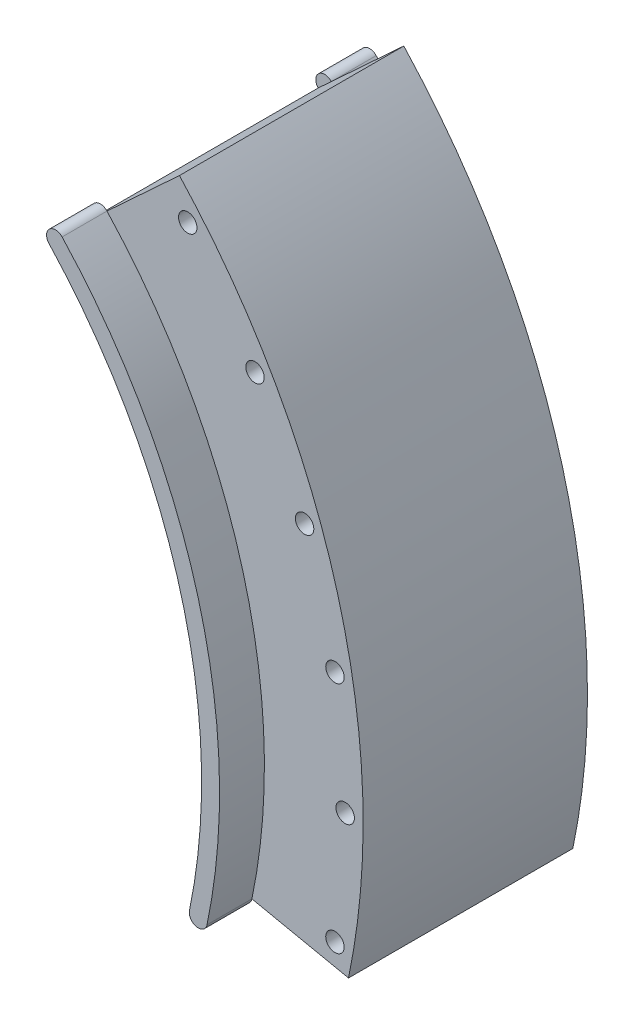
SolidWorks part; units mm, degrees
material "ABS"
ref_plane "Front Plane" through (0, 0, 0) normal (0, 0, 1) x (1, 0, 0)
ref_plane "Top Plane" through (0, 0, 0) normal (0, 1, 0) x (1, 0, 0)
ref_plane "Right Plane" through (0, 0, 0) normal (1, 0, 0) x (0, 0, -1)
sketch "Sketch1" plane through (0, 0, 0) normal (0, 0, 1) x (1, 0, 0)
  line L0 (0, 0) -> (203.2, 0) construction
  line L1 (203.2, 0) -> (209.55, 0) construction
  line L2 (148.1742, 148.1742) -> (143.6841, 143.6841) construction
  line L3 (143.6841, 143.6841) -> (0, 0) construction
  line L4 (203.2, 0) -> (203.2, -50.8) construction
  line L5 (198.9038, -41.5636) -> (205.1195, -42.8625) construction
  line L6 (198.9038, -41.5636) -> (0, 0) construction
  line L7 (203.2, -50.8) -> (205.829, -50.8) construction
  line L8 (149.1871, 137.9618) -> (153.8492, 142.2731) construction
  line L9 (149.1871, 137.9618) -> (0, 0) construction
  arc A0 (203.2, 0) -> (149.1871, 137.9618) centre (0, 0) ccw
  arc A1 (209.55, 0) -> (153.8492, 142.2731) centre (0, 0) ccw
  arc A2 (203.2, 0) -> (198.9038, -41.5636) centre (0, 0) cw
  arc A3 (198.9038, -41.5636) -> (205.1195, -42.8625) centre (202.0116, -42.2131) ccw
  arc A4 (205.1195, -42.8625) -> (209.55, 0) centre (0, 0) ccw
  arc A5 (149.1871, 137.9618) -> (153.8492, 142.2731) centre (151.5181, 140.1174) cw
  arc A6 (149.1871, 137.9618) -> (143.6841, 143.6841) centre (0, 0) ccw construction
  arc A7 (153.8492, 142.2731) -> (148.1742, 148.1742) centre (0, 0) ccw construction
  dimension "D1" = 203.2
  dimension "D2" = 45
  dimension "D3" = 6.35
  dimension "D4" = 50.8
  dimension "D5" = 7.9375
  dimension "D6" = 7.9375
extrude "Boss-Extrude2" add sketch "Sketch1" along normal blind 15.875 contours A5 A0 A2 A3 A4 A1 region at (191.0626, 74.8022, 0)
sketch "Sketch3" plane through (0, 0, 15.875) normal (0, 0, 1) x (1, 0, 0)
  line L0 (0, 0) -> (238.125, 0) construction
  line L1 (0, 0) -> (238.125, 0) construction
  line L2 (0, 0) -> (234.5073, 41.35) construction
  line L3 (0, 0) -> (238.125, 0) construction
  line L4 (0, 0) -> (234.5073, -41.35) construction
  line L5 (149.1871, 137.9618) -> (179.4907, 165.9853)
  line L6 (149.1871, 137.9618) -> (0, 0) construction
  line L7 (198.9038, -41.5636) -> (239.3061, -50.0062)
  line L8 (198.9038, -41.5636) -> (0, 0) construction
  circle A0 centre (238.125, 0) radius 3.2639
  circle A1 centre (234.5073, 41.35) radius 3.2639
  circle A2 centre (223.7643, 81.4435) radius 3.2639
  circle A3 centre (206.2223, 119.0625) radius 3.2639
  circle A4 centre (182.4143, 153.0638) radius 3.2639
  circle A5 centre (234.5073, -41.35) radius 3.2639
  arc A6 (198.9038, -41.5636) -> (149.1871, 137.9618) centre (0, 0) ccw construction
  arc A7 (198.9038, -41.5636) -> (149.1871, 137.9618) centre (0, 0) ccw
  arc A8 (179.4907, 165.9853) -> (239.3061, -50.0062) centre (0, 0) cw
  dimension "D2" = 6.5278
  dimension "D7" = 244.475
  dimension "D1" = 238.125
  dimension "D4" = 10
  dimension "D6" = 10
  dimension "D3" = 5
  dimension "D5" = 2
extrude "Boss-Extrude3" add sketch "Sketch3" along normal blind 79.375
ref_plane "Plane1" through (0, 0, 55.5625) normal (0, 0, -1) x (-1, 0, 0)
mirror "Mirror1" about plane through (0, 0, 55.5625) normal (0, 0, -1) of "Boss-Extrude2"
